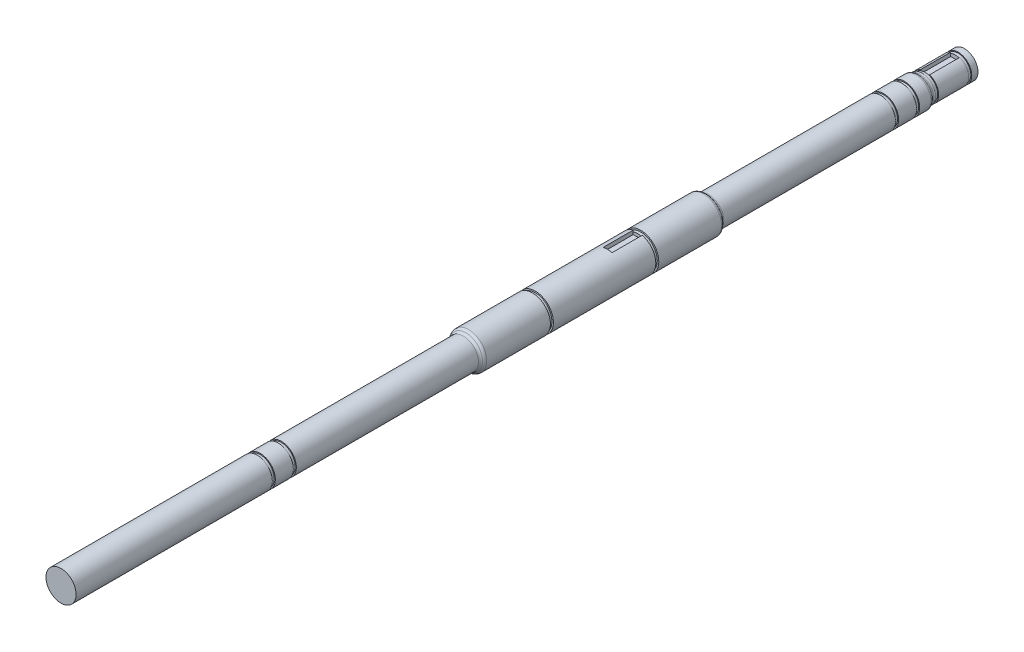
SolidWorks part; units mm, degrees
ref_plane "Front Plane" through (0, 0, 0) normal (0, 0, 1) x (1, 0, 0)
ref_plane "Top Plane" through (0, 0, 0) normal (0, 1, 0) x (1, 0, 0)
ref_plane "Right Plane" through (0, 0, 0) normal (1, 0, 0) x (0, 0, -1)
sketch "Sketch1" plane through (0, 0, 0) normal (1, 0, 0) x (0, 0, -1)
  line L0 (-134.9921, 0) -> (165.0079, 0)
  line L1 (-134.9921, 0) -> (-134.9921, 5)
  line L2 (165.0079, 0) -> (165.0079, 4.5)
  line L3 (165.0079, 4.5) -> (149.3574, 4.5)
  line L4 (149.3574, 4.5) -> (149.3574, 5)
  line L5 (149.3574, 5) -> (59.3574, 5)
  line L6 (59.3574, 5) -> (59.3574, 6)
  line L7 (59.3574, 6) -> (19.3574, 6)
  line L8 (19.3574, 6) -> (19.3574, 5)
  line L9 (-134.9921, 5) -> (19.3574, 5)
  dimension "D1" = 300
  dimension "D2" = 5
  dimension "D3" = 4.5
  dimension "D4" = 0.5
  dimension "D5" = 90
  dimension "D6" = 1
  dimension "D7" = 40
  dimension "D8" = 1
revolve "Revolve1" add sketch "Sketch1" angle 360 about L0
sketch "Sketch7" plane through (0, 0, 0) normal (1, 0, 0) x (0, 0, -1)
  line L0 (59.3574, 6) -> (19.3574, 6) construction
  line L1 (56.5122, 6) -> (46.5122, 6)
  line L2 (56.5122, 6) -> (56.5122, 4.5)
  line L3 (56.5122, 4.5) -> (46.5122, 4.5)
  line L4 (46.5122, 6) -> (46.5122, 4.5)
  dimension "D1" = 1.5
  dimension "D2" = 10
extrude "Cut-Extrude4" cut sketch "Sketch7" against normal mid plane 3
sketch "Sketch8" plane through (0, 0, 0) normal (1, 0, 0) x (0, 0, -1)
  line L0 (165.0079, 4.5) -> (149.3574, 4.5) construction
  line L1 (161.9345, 4.5) -> (151.9345, 4.5)
  line L2 (161.9345, 4.5) -> (161.9345, 3)
  line L3 (161.9345, 3) -> (151.9345, 3)
  line L4 (151.9345, 4.5) -> (151.9345, 3)
  dimension "D1" = 10
  dimension "D2" = 1.5
extrude "Cut-Extrude5" cut sketch "Sketch8" against normal mid plane 3
ref_plane "Plane1" through (0, 0, -144.6474) normal (0, 0, -1) x (-1, 0, 0)
ref_plane "Plane2" through (0, 0, -137.6474) normal (0, 0, -1) x (-1, 0, 0)
sketch "Sketch9" plane through (0, 0, -144.6474) normal (0, 0, -1) x (-1, 0, 0)
  circle A0 centre (0, 0) radius 5
sketch "Sketch10" plane through (0, 0, -137.6474) normal (0, 0, -1) x (-1, 0, 0)
  circle A0 centre (0, 0) radius 5
sketch "Sketch11" plane through (0, 0, 0) normal (1, 0, 0) x (0, 0, -1)
  line L0 (149.3574, 5) -> (59.3574, 5) construction
  line L1 (137.1498, 5) -> (138.1498, 5)
  line L2 (137.1498, 5) -> (137.1498, 4.65)
  line L3 (137.1498, 4.65) -> (138.1498, 4.65)
  line L4 (138.1498, 5) -> (138.1498, 4.65)
  dimension "D1" = 0.35
  dimension "D2" = 1
sweep "Cut-Sweep1" cut profiles "Sketch11" path "Sketch10"
sketch "Sketch12" plane through (0, 0, 0) normal (1, 0, 0) x (0, 0, -1)
  line L0 (149.3574, 5) -> (138.1498, 5) construction
  line L1 (144.1481, 5) -> (145.1481, 5)
  line L2 (144.1481, 5) -> (144.1481, 4.65)
  line L3 (144.1481, 4.65) -> (145.1481, 4.65)
  line L4 (145.1481, 5) -> (145.1481, 4.65)
  dimension "D1" = 0.35
  dimension "D2" = 1
sweep "Cut-Sweep2" cut profiles "Sketch12" path "Sketch9"
ref_plane "Plane3" through (0, 0, -59.3574) normal (0, 0, -1) x (-1, 0, 0)
sketch "Sketch14" plane through (0, 0, -59.3574) normal (0, 0, -1) x (-1, 0, 0)
  circle A0 centre (0, 0) radius 6
extrude "Boss-Extrude1" add sketch "Sketch14" along normal blind 20
ref_plane "Plane4" through (0, 0, -19.3574) normal (0, 0, 1) x (1, 0, 0)
sketch "Sketch15" plane through (0, 0, -19.3574) normal (0, 0, 1) x (1, 0, 0)
  circle A0 centre (0, 0) radius 6
extrude "Boss-Extrude2" add sketch "Sketch15" along normal blind 20
ref_plane "Plane5" through (0, 0, 62.3526) normal (0, 0, -1) x (-1, 0, 0)
sketch "Sketch16" plane through (0, 0, 62.3526) normal (0, 0, -1) x (-1, 0, 0)
  circle A0 centre (0, 0) radius 5
ref_plane "Plane6" through (0, 0, 69.3526) normal (0, 0, -1) x (-1, 0, 0)
sketch "Sketch17" plane through (0, 0, 69.3526) normal (0, 0, -1) x (-1, 0, 0)
  circle A0 centre (0, 0) radius 5
sketch "Sketch18" plane through (0, 0, 0) normal (1, 0, 0) x (0, 0, -1)
  line L0 (-0.6426, 5) -> (-134.9921, 5) construction
  line L1 (-62.8543, 5) -> (-61.8543, 5)
  line L2 (-62.8543, 5) -> (-62.8543, 4.65)
  line L3 (-62.8543, 4.65) -> (-61.8543, 4.65)
  line L4 (-61.8543, 5) -> (-61.8543, 4.65)
  dimension "D1" = 0.35
  dimension "D2" = 1
sweep "Cut-Sweep3" cut profiles "Sketch18" path "Sketch16"
sketch "Sketch19" plane through (0, 0, 0) normal (1, 0, 0) x (0, 0, -1)
  line L0 (-62.8543, 5) -> (-134.9921, 5) construction
  line L1 (-69.8285, 5) -> (-68.8285, 5)
  line L2 (-69.8285, 5) -> (-69.8285, 4.65)
  line L3 (-69.8285, 4.65) -> (-68.8285, 4.65)
  line L4 (-68.8285, 5) -> (-68.8285, 4.65)
  dimension "D1" = 0.35
  dimension "D2" = 1
sweep "Cut-Sweep4" cut profiles "Sketch19" path "Sketch17"
ref_plane "Plane7" through (0, 0, -57.0122) normal (0, 0, 1) x (1, 0, 0)
sketch "Sketch20" plane through (0, 0, -57.0122) normal (0, 0, 1) x (1, 0, 0)
  circle A0 centre (0, 0) radius 6
sketch "Sketch22" plane through (0, 0, 0) normal (1, 0, 0) x (0, 0, -1)
  line L0 (79.3574, 6) -> (56.5122, 6) construction
  line L1 (56.5122, 6) -> (57.5083, 6)
  line L2 (56.5122, 6) -> (56.5122, 5.5)
  line L3 (56.5122, 5.5) -> (57.5083, 5.5)
  line L4 (57.5083, 6) -> (57.5083, 5.5)
  dimension "D1" = 0.5
sweep "Cut-Sweep5" cut profiles "Sketch22" path "Sketch20"
ref_plane "Plane9" through (0, 0, -151.4345) normal (0, 0, -1) x (-1, 0, 0)
ref_plane "Plane10" through (0, 0, -162.4345) normal (0, 0, 1) x (1, 0, 0)
sketch "Sketch24" plane through (0, 0, -162.4345) normal (0, 0, 1) x (1, 0, 0)
  circle A0 centre (0, 0) radius 4.5
sketch "Sketch25" plane through (0, 0, -151.4345) normal (0, 0, -1) x (-1, 0, 0)
  circle A0 centre (0, 0) radius 4.5
sketch "Sketch26" plane through (0, 0, 0) normal (1, 0, 0) x (0, 0, -1)
  line L0 (165.0079, 4.5) -> (161.9345, 4.5) construction
  line L1 (161.9345, 4.5) -> (162.9346, 4.5)
  line L2 (161.9345, 4.5) -> (161.9345, 4.2)
  line L3 (161.9345, 4.2) -> (162.9346, 4.2)
  line L4 (162.9346, 4.5) -> (162.9346, 4.2)
  dimension "D1" = 0.3
sweep "Cut-Sweep7" cut profiles "Sketch26" path "Sketch24"
sketch "Sketch27" plane through (0, 0, 0) normal (1, 0, 0) x (0, 0, -1)
  line L0 (151.9345, 4.5) -> (149.3574, 4.5) construction
  line L1 (151.9345, 4.5) -> (150.934, 4.5)
  line L2 (151.9345, 4.5) -> (151.9345, 4.2)
  line L3 (151.9345, 4.2) -> (150.934, 4.2)
  line L4 (150.934, 4.5) -> (150.934, 4.2)
  dimension "D1" = 0.3
sweep "Cut-Sweep8" cut profiles "Sketch27" path "Sketch25"
ref_plane "Plane11" through (0, 0, -22.0122) normal (0, 0, 1) x (1, 0, 0)
sketch "Sketch28" plane through (0, 0, -22.0122) normal (0, 0, 1) x (1, 0, 0)
  circle A0 centre (0, 0) radius 6
sketch "Sketch29" plane through (0, 0, 0) normal (1, 0, 0) x (0, 0, -1)
  line L0 (46.5122, 6) -> (-0.6426, 6) construction
  line L1 (21.5132, 6) -> (22.5132, 6)
  line L2 (21.5132, 6) -> (21.5132, 5.5)
  line L3 (21.5132, 5.5) -> (22.5132, 5.5)
  line L4 (22.5132, 6) -> (22.5132, 5.5)
  dimension "D1" = 1
  dimension "D2" = 0.5
sweep "Cut-Sweep9" cut profiles "Sketch29" path "Sketch28"
fillet "Fillet2" radius 1 1 edges at (4.5, 0, -149.3574)
fillet "Fillet3" radius 1 1 edges at (5, 0, -149.3574)
fillet "Fillet4" radius 1 1 edges at (-6, 0, -79.3574)
fillet "Fillet5" radius 1 1 edges at (-5, 0, -79.3574)
fillet "Fillet6" radius 1 1 edges at (6, 0, 0.6426)
fillet "Fillet7" radius 1 1 edges at (5, 0, 0.6426)
